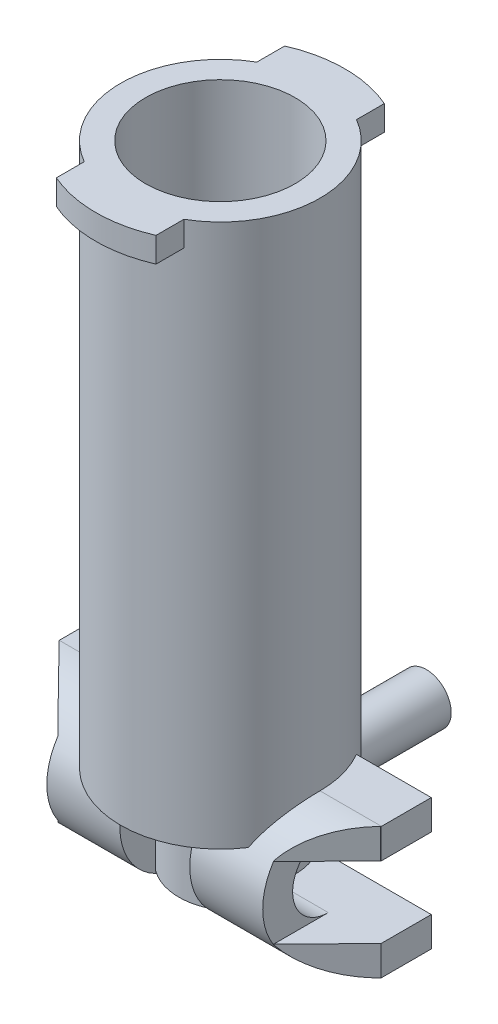
SolidWorks part; units mm, degrees
ref_plane "Front Plane" through (0, 0, 0) normal (0, 0, 1) x (1, 0, 0)
ref_plane "Top Plane" through (0, 0, 0) normal (0, 1, 0) x (1, 0, 0)
ref_plane "Right Plane" through (0, 0, 0) normal (1, 0, 0) x (0, 0, -1)
sketch "Sketch1" plane through (0, 0, 0) normal (0, 1, 0) x (1, 0, 0)
  circle A0 centre (0, 0) radius 6
extrude "Boss-Extrude1" add sketch "Sketch1" along normal blind 32.7
shell "Shell1" thickness 1.5
sketch "Sketch2" plane through (0, 0, 0) normal (0, -1, 0) x (1, 0, 0)
  circle A3 centre (0, -1) radius 3.5
extrude "Boss-Extrude3" add sketch "Sketch2" along normal blind 5.5 contours A3
shell "Shell3" thickness 1.5
sketch "Sketch4" plane through (0, 0, 0) normal (0, 0, 1) x (1, 0, 0)
  circle A0 centre (0, -2.5735) radius 2.5
extrude "Boss-Extrude4" add sketch "Sketch4" against normal blind 6.1
sketch "Sketch7" plane through (0, 0, -6.1) normal (0, 0, -1) x (-1, 0, 0)
  circle A0 centre (0, -2.5735) radius 1.5
extrude "Boss-Extrude6" add sketch "Sketch7" along normal blind 6.3
sketch "Sketch8" plane through (0, 0, -12.4) normal (0, 0, -1) x (-1, 0, 0)
  circle A0 centre (0, -2.5735) radius 0.95
extrude "Cut-Extrude1" cut sketch "Sketch8" against normal blind 12.3
sketch "Sketch9" plane through (0, -4, 0) normal (0, 1, 0) x (1, 0, 0)
  circle A0 centre (0, 1) radius 2
extrude "Cut-Extrude2" cut sketch "Sketch9" along normal through all contours A0
sketch "Sketch10" plane through (0, 0, 0) normal (1, 0, 0) x (0, 0, -1)
  line L1 (0, -4.3) -> (0, -6.098)
  line L2 (0, -4.3) -> (0, -6.9944) construction
  line L3 (0, 1.798) -> (0, 0)
  arc A0 (0, 0) -> (0, -4.3) centre (0, -2.15) ccw
  arc A1 (0, 1.798) -> (0, -6.098) centre (0, -2.15) ccw
extrude "Boss-Extrude7" add sketch "Sketch10" along normal blind 6.5 contours L3 A0 L1 A1
sketch "Sketch11" plane through (0, -5.5, 0) normal (0, -1, 0) x (1, 0, 0)
  line L0 (0, 0) -> (2.1, 0)
  line L1 (0, 0) -> (3.3541, 0) construction
  line L2 (2.1, 0) -> (2.1, 4.7594)
  line L3 (2.1, 4.7594) -> (0, 4.7594)
  line L4 (0, 4.7594) -> (0, 0)
extrude "Cut-Extrude3" cut sketch "Sketch11" along normal through all contours L4 L0 L2 L3
sketch "Sketch12" plane through (0, 0, 0) normal (0, -1, 0) x (1, 0, 0)
  line L0 (2.1057, 1.7957) -> (2.1057, 3.948)
  line L1 (6.5, 3.948) -> (0, 3.948) construction
  line L2 (2.1057, 3.948) -> (0, 3.948)
  line L3 (0, 3.948) -> (0, 2.5)
  arc A0 (2.1057, 1.7957) -> (0, 2.5) centre (0, -1) ccw
extrude "Cut-Extrude4" cut sketch "Sketch12" along normal through all
sketch "Sketch13" plane through (0, 0, 0) normal (0, 0, -1) x (-1, 0, 0)
  line L0 (-6.5, -4.3) -> (-6.5, -6.098)
  line L1 (-6.5, -4.3) -> (-2.1, -4.3)
  line L2 (-6.5, -6.098) -> (-2.1, -6.098)
  line L3 (-2.1, -4.3) -> (-2.1, -6.098)
extrude "Boss-Extrude8" add sketch "Sketch13" along normal blind 3 contours L0 L1 L3 L2
sketch "Sketch15" plane through (0, 0, 0) normal (0, 0, -1) x (-1, 0, 0)
  line L1 (-6.5, 1.798) -> (-6.5, 0)
  line L2 (-6.5, 1.798) -> (-2.1039, 1.798)
  line L3 (-6.5, 0) -> (-2.1039, 0)
  line L4 (-2.1039, 1.798) -> (-2.1039, 0)
extrude "Boss-Extrude9" add sketch "Sketch15" along normal blind 3
sketch "Sketch16" plane through (0, -4, 0) normal (0, 1, 0) x (1, 0, 0)
  circle A0 centre (0, 1) radius 2
extrude "Cut-Extrude5" cut sketch "Sketch16" along normal through all
sketch "Sketch17" plane through (0, 1.5, 0) normal (0, 1, 0) x (1, 0, 0)
  circle A0 centre (0, 0) radius 4.5
extrude "Cut-Extrude6" cut sketch "Sketch17" along normal through all
sketch "Sketch18" plane through (6.5, 0, 0) normal (1, 0, 0) x (0, 0, -1)
  line L0 (3, 1.798) -> (3, 0)
  line L1 (3, 1.798) -> (-0.0248, 1.798)
  line L2 (3, 0) -> (-0.0248, 0)
  line L3 (-0.0248, 1.798) -> (-0.0248, 0)
  line L4 (-3.948, -2.15) -> (-2.15, -2.15) construction
  line L5 (3, -4.3) -> (-0.0248, -4.3)
  line L6 (-0.0248, -6.098) -> (-0.0248, -4.3)
  line L7 (3, -6.098) -> (-0.0248, -6.098)
  line L8 (3, -6.098) -> (3, -4.3)
  arc A0 (0, 1.798) -> (0, -6.098) centre (0, -2.15) ccw construction
  arc A1 (0, 0) -> (0, -4.3) centre (0, -2.15) ccw construction
extrude "Boss-Extrude10" add sketch "Sketch18" along normal blind 3.2
sketch "Sketch19" plane through (0, -4.3, 0) normal (0, 1, 0) x (1, 0, 0)
  line L0 (6.5, -3.2856) -> (6.5, 0)
  line L1 (6.5, 0) -> (9.7, -0.0248)
  line L4 (6.5, -3.2856) -> (9.7, -0.0248)
extrude "Boss-Extrude11" add sketch "Sketch19" against normal up to surface (1.798 mm away) up to face at (6.1, -6.098, -0.9917)
sketch "Sketch22" plane through (6.5, 0, 0) normal (-1, 0, 0) x (0, 0, 1)
  line L0 (0, -6.098) -> (3.2856, -6.098)
  line L1 (3.2856, -6.098) -> (3.2856, -4.3389)
  arc A0 (0, -6.098) -> (3.2856, -4.3389) centre (0, -2.15) ccw
extrude "Cut-Extrude11" cut sketch "Sketch22" against normal through all
sketch "Sketch24" plane through (0, 0, 0) normal (0, -1, 0) x (1, 0, 0)
  line L0 (9.7, 0) -> (6.5, 3.2856)
  line L1 (6.5, 3.2856) -> (6.5, 0.0124)
  line L2 (6.5, 0.0248) -> (6.5, 0) construction
  line L3 (6.5, 0.0124) -> (9.7, 0)
extrude "Boss-Extrude12" add sketch "Sketch24" against normal up to surface (1.798 mm away) up to face at (7.2989, 1.798, -1.0006)
sketch "Sketch25" plane through (6.5, 0, 0) normal (-1, 0, 0) x (0, 0, 1)
  line L0 (3.2856, 1.798) -> (0, 1.798)
  line L1 (3.2856, 1.798) -> (3.2856, 0)
  arc A2 (3.2856, 0.0389) -> (0, 1.798) centre (0, -2.15) ccw
  arc M1 (0.0248, 1.7979) -> (3.2856, 0.0389) centre (0, -2.15) cw
  line M2 (3.2856, 0.0389) -> (3.2856, 1.798)
  line M3 (3.2856, 1.798) -> (0.0248, 1.7979)
extrude "Cut-Extrude12" cut sketch "Sketch25" against normal through all contours A2 L0 M1 M2 M3
mirror "Mirror3" about plane through (0, 0, 0) normal (1, 0, 0) of bodies 125
sketch "Sketch26" plane through (0, 32.7, 0) normal (0, 1, 0) x (1, 0, 0)
  line L1 (3, 5.1962) -> (3, 6.8739)
  line L4 (-3, 5.1962) -> (-3, 6.8739)
  line L5 (3, -5.1962) -> (3, -6.8739)
  line L6 (-3, -5.1962) -> (-3, -6.8739)
  arc A0 (3, 6.8739) -> (-3, 6.8739) centre (0, 0) ccw
  arc A1 (3, 5.1962) -> (-3, 5.1962) centre (0, 0) ccw
  arc A2 (3, -6.8739) -> (-3, -6.8739) centre (0, 0) cw
  arc A3 (3, -5.1962) -> (-3, -5.1962) centre (0, 0) cw
extrude "Boss-Extrude13" add sketch "Sketch26" against normal blind 1.5
